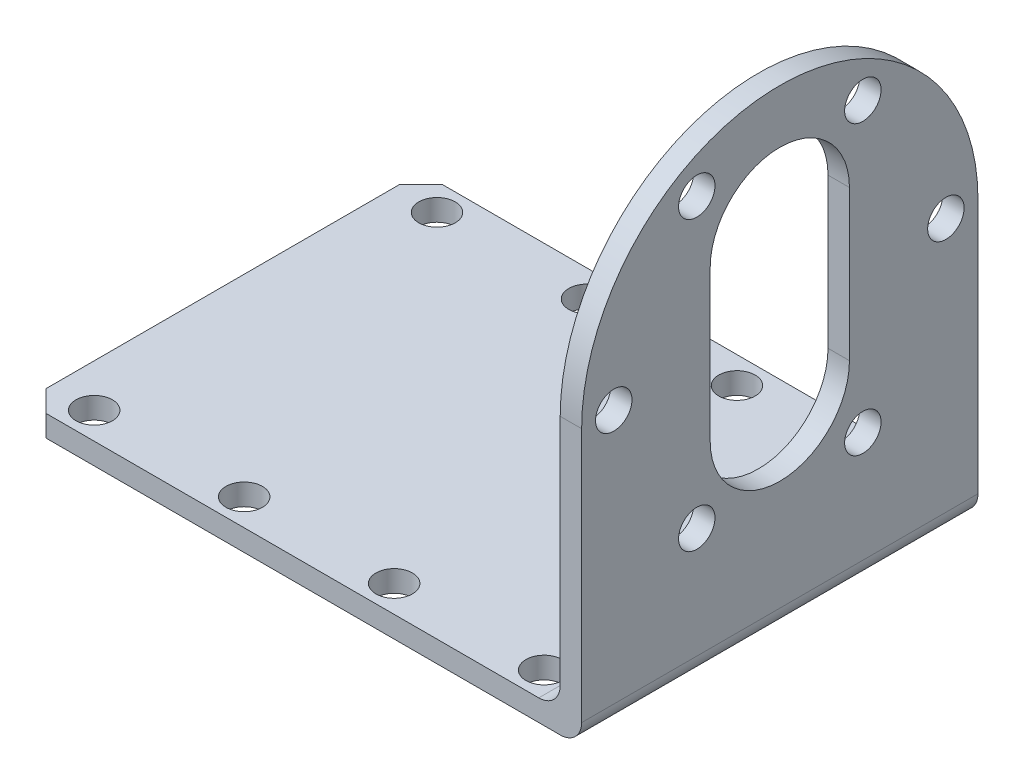
SolidWorks part; units mm, degrees
ref_plane "Alzado" through (0, 0, 0) normal (0, 0, 1) x (1, 0, 0)
ref_plane "Planta" through (0, 0, 0) normal (0, 1, 0) x (1, 0, 0)
ref_plane "Vista lateral" through (0, 0, 0) normal (1, 0, 0) x (0, 0, -1)
sketch "Croquis1" plane through (0, 0, 0) normal (0, 1, 0) x (1, 0, 0)
  line L1 (-26, 18.5) -> (26, 18.5)
  line L2 (-26, 18.5) -> (-26, -18.5)
  line L3 (-26, -18.5) -> (26, -18.5)
  line L4 (26, 18.5) -> (26, -18.5)
  line L5 (-26, 18.5) -> (26, -18.5) construction
  line L6 (-26, -18.5) -> (26, 18.5) construction
  point P0 (0, 0)
  dimension "D1" = 37
  dimension "D2" = 52
extrude "Saliente-Extruir1" add sketch "Croquis1" along normal blind 2
sketch "Croquis6" plane through (0, 2, 0) normal (0, 1, 0) x (1, 0, 0)
  line L0 (-26, 0) -> (26, 0) construction
  line L1 (-26, 18.5) -> (-26, -18.5) construction
  line L2 (26, -18.5) -> (26, 18.5) construction
  line L3 (-26, 16) -> (26, 16) construction
  line L4 (-26, -16) -> (26, -16) construction
  point P10 (-22, 16)
  point P11 (-8, 16)
  point P12 (6, 16)
  point P13 (20, 16)
  point P14 (-22, -16)
  point P15 (-8, -16)
  point P16 (6, -16)
  point P17 (20, -16)
  dimension "D1" = 16
  dimension "D2" = 16
  dimension "D3" = 4
  dimension "D4" = 14
  dimension "D5" = 14
  dimension "D6" = 14
hole_wizard "Taladro de margen para M33" positions "Croquis7" profile "Croquis8" hole size "M3" standard "Ansi Metric" end condition through all
sketch "Croquis7" plane through (0, 2, 0) normal (0, 1, 0) x (1, 0, 0)
  point P0 (-22, 16)
  point P3 (-8, 16)
  point P6 (6, 16)
  point P9 (20, 16)
  point P12 (-22, -16)
  point P15 (-8, -16)
  point P18 (6, -16)
  point P21 (20, -16)
sketch "Croquis8" plane through (-22, 2, -16) normal (1, 0, 0) x (0, 0, 1)
  line L0 (0, 0) -> (0, 2)
  line L1 (0, 2) -> (1.7, 2)
  line L2 (1.7, 2) -> (1.7, 0)
  line L5 (1.7, 0) -> (0, 0)
  line L11 (0, -6.35) -> (0, 107.95) construction
  dimension "Diámetro de taladro hasta el siguiente" = 3.4
  dimension "Profundidad de taladro hasta el siguiente" = 2
sketch "Croquis9" plane through (0, 2, 0) normal (0, 1, 0) x (1, 0, 0)
  line L0 (-26, -18.5) -> (26, -18.5) construction
  line L1 (26, 18.5) -> (24, 18.5)
  line L2 (26, 18.5) -> (26, -18.5)
  line L3 (26, -18.5) -> (24, -18.5)
  line L4 (24, 18.5) -> (24, -18.5)
  dimension "D1" = 2
extrude "Saliente-Extruir2" add sketch "Croquis9" along normal blind 42.26
chamfer "Chaflán1" distance 2 angle 45 2 edges at (-26, 1, 18.5) (-26, 1, -18.5)
fillet "Redondeo1" 2 edges at (25, 44.26, 18.5) (25, 44.26, -18.5) type full round first side face at (8.6667, 15.42, 18.5) second side face at (8.6667, 15.42, -18.5) middle face at (25, 44.26, 0)
sketch "Croquis12" plane through (24, 0, 0) normal (-1, 0, 0) x (0, 0, 1)
  circle A0 centre (0, 25.76) radius 15.5 construction
  point P3 (-15.5, 25.76)
  point P7 (-7.75, 39.1834)
  point P8 (7.75, 39.1834)
  point P9 (15.5, 25.76)
  point P10 (7.75, 12.3366)
  point P11 (-7.75, 12.3366)
  dimension "D1" = 31
  dimension "D2" = 6
hole_wizard "Taladro de margen para M34" positions "Croquis13" profile "Croquis14" hole size "M3" standard "Ansi Metric" end condition through all
sketch "Croquis13" plane through (24, 0, 0) normal (-1, 0, 0) x (0, 0, 1)
  point P0 (-15.5, 25.76)
  point P3 (-7.75, 39.1834)
  point P6 (7.75, 39.1834)
  point P9 (15.5, 25.76)
  point P12 (7.75, 12.3366)
  point P15 (-7.75, 12.3366)
sketch "Croquis14" plane through (24, 25.76, -15.5) normal (0, 1, 0) x (0, 0, 1)
  line L0 (0, 0) -> (0, 2)
  line L1 (0, 2) -> (1.7, 2)
  line L2 (1.7, 2) -> (1.7, 0)
  line L5 (1.7, 0) -> (0, 0)
  line L11 (0, -6.35) -> (0, 107.95) construction
  dimension "Diámetro de taladro hasta el siguiente" = 3.4
  dimension "Profundidad de taladro hasta el siguiente" = 2
sketch "Croquis15" plane through (24, 0, 0) normal (-1, 0, 0) x (0, 0, 1)
  line L0 (0, 25.76) -> (0, 18.76) construction
  line L1 (0, 25.76) -> (0, 32.76) construction
  line L2 (-6.5, 18.76) -> (-6.5, 32.76)
  line L3 (6.5, 18.76) -> (6.5, 32.76)
  arc A0 (6.5, 32.76) -> (-6.5, 32.76) centre (0, 32.76) ccw
  arc A1 (-6.5, 18.76) -> (6.5, 18.76) centre (0, 18.76) ccw
  dimension "D3" = 13
  dimension "D1" = 7
  dimension "D2" = 7
extrude "Cortar-Extruir1" cut sketch "Croquis15" against normal through all
fillet "Redondeo3" radius 2 1 edges at (26, 0, 0)
fillet "Redondeo4" radius 2 1 edges at (24, 2, 0)
